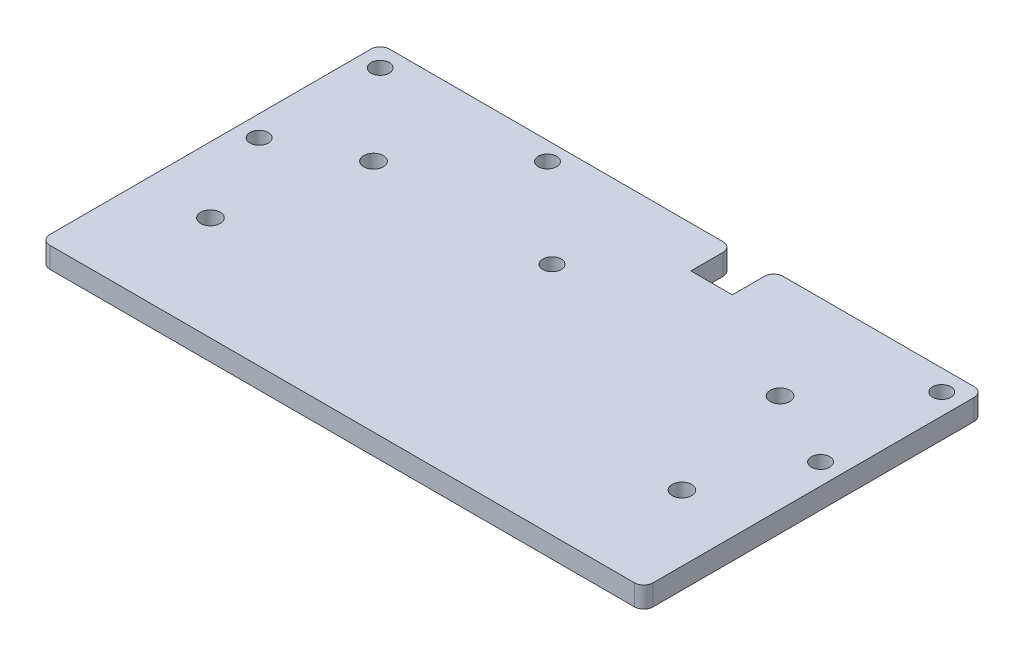
SolidWorks part; units mm, degrees
ref_plane "Front Plane" through (0, 0, 0) normal (0, 0, 1) x (1, 0, 0)
ref_plane "Top Plane" through (0, 0, 0) normal (0, 1, 0) x (1, 0, 0)
ref_plane "Right Plane" through (0, 0, 0) normal (1, 0, 0) x (0, 0, -1)
sketch "Sketch1" plane through (0, 0, 0) normal (0, 1, 0) x (1, 0, 0)
  line L0 (-65, 0) -> (65, 0) construction
  line L1 (63, 20.3) -> (21.8, 20.3)
  line L2 (65, 18.3) -> (65, -50.9)
  line L3 (63, -52.9) -> (-63, -52.9)
  line L4 (-65, 18.3) -> (-65, -50.9)
  line L5 (-65, -14.8) -> (65, -14.8) construction
  line L6 (-65, -46.169) -> (65, -46.169) construction
  line L7 (-50.8, -14.8) -> (-50.8, -46.169) construction
  line L8 (10.87, 18.3) -> (10.87, 11.37)
  line L9 (10.87, 11.37) -> (19.8, 11.37)
  line L10 (19.8, 18.3) -> (19.8, 11.37)
  line L11 (0, 20.3) -> (0, -52.9) construction
  line L12 (8.87, 20.3) -> (-63, 20.3)
  line L13 (-43.8023, -14.8) -> (-43.8023, 20.3) construction
  line L14 (-5.3283, -2.3397) -> (-43.8023, -2.3397) construction
  circle A0 centre (-60.5, 15.8) radius 1.975
  circle A1 centre (60.5, 15.8) radius 1.975
  circle A2 centre (60.5, -10.3) radius 1.975
  circle A3 centre (-60.5, -10.3) radius 1.975
  circle A4 centre (-25.0043, 16.35) radius 1.975
  arc A5 (10.87, 18.3) -> (8.87, 20.3) centre (8.87, 18.3) ccw
  circle A6 centre (-5.3283, -2.3397) radius 1.975
  arc A7 (63, 20.3) -> (65, 18.3) centre (63, 18.3) cw
  arc A8 (21.8, 20.3) -> (19.8, 18.3) centre (21.8, 18.3) ccw
  arc A9 (-63, 20.3) -> (-65, 18.3) centre (-63, 18.3) ccw
  arc A10 (65, -50.9) -> (63, -52.9) centre (63, -50.9) cw
  arc A11 (-63, -52.9) -> (-65, -50.9) centre (-63, -50.9) cw
  circle A12 centre (-50.8, -30.4845) radius 2.1082
  circle A13 centre (50.8, -30.4845) radius 2.1082
  circle A14 centre (-43.8023, -2.3397) radius 2.1082
  circle A15 centre (43.8023, -2.3397) radius 2.1082
  point P0 (0, 0)
  point P26 (10.87, 20.3)
  point P31 (65, 20.3)
  point P36 (-65, 20.3)
  dimension "D6" = 3.95
  dimension "D9" = 3.95
  dimension "D12" = 2
  dimension "D13" = 3.95
  dimension "D16" = 3.95
  dimension "D20" = 2
  dimension "D21" = 2
  dimension "D24" = 4.2164
  dimension "D27" = 4.2164
  dimension "D1" = 130
  dimension "D2" = 30.6
  dimension "D3" = 8.93
  dimension "D4" = 8.93
  dimension "D5" = 45.2
  dimension "D7" = 4.5
  dimension "D8" = 4.5
  dimension "D10" = 35.5
  dimension "D11" = 3.95
  dimension "D14" = 73.2
  dimension "D15" = 4.5
  dimension "D17" = 4.6793
  dimension "D18" = 5.3283
  dimension "D19" = 20.3
  dimension "D22" = 38.1
  dimension "D23" = 31.369
  dimension "D25" = 50.8
  dimension "D26" = 43.8023
  dimension "D28" = 38.474
extrude "Boss-Extrude1" add sketch "Sketch1" along normal blind 4.5
